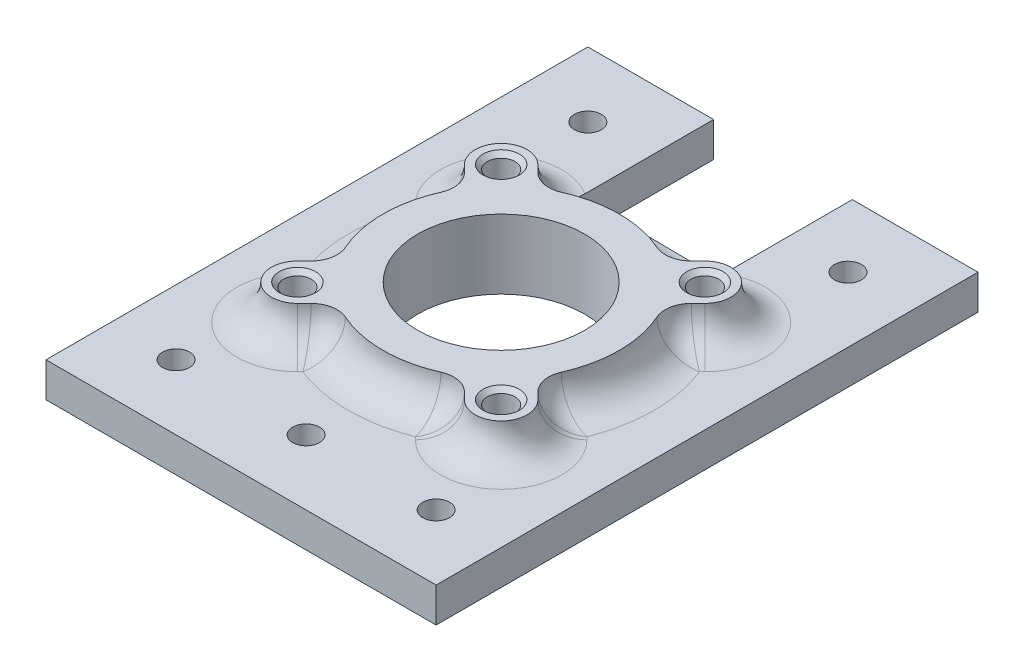
SolidWorks part; units mm, degrees
material "PET"
ref_plane "Front Plane" through (0, 0, 0) normal (0, 0, 1) x (1, 0, 0)
ref_plane "Top Plane" through (0, 0, 0) normal (0, 1, 0) x (1, 0, 0)
ref_plane "Right Plane" through (0, 0, 0) normal (1, 0, 0) x (0, 0, -1)
sketch "Sketch1" plane through (0, 0, 0) normal (0, 1, 0) x (1, 0, 0)
  line L1 (-45, 65) -> (45, 65)
  line L2 (-45, 65) -> (-45, -60)
  line L3 (-45, -60) -> (45, -60)
  line L4 (45, 65) -> (45, -60)
  circle A0 centre (0, 0) radius 19.25
  point P0 (0, 0)
  dimension "D4" = 38.5
  dimension "D1" = 90
  dimension "D2" = 125
  dimension "D3" = 45
  dimension "D5" = 65
extrude "Boss-Extrude1" add sketch "Sketch1" along normal blind 8
sketch "Sketch5" plane through (0, 8, 0) normal (0, 1, 0) x (1, 0, 0)
  circle A0 centre (0, 0) radius 19.25
  circle A1 centre (0, 0) radius 27.25
  dimension "D1" = 38.5
  dimension "D2" = 8
extrude "Boss-Extrude2" add sketch "Sketch5" along normal blind 8
sketch "Sketch9" plane through (0, 8, 0) normal (0, 1, 0) x (1, 0, 0)
  line L0 (17.6998, 26.1624) -> (19.2687, 27.7313)
  line L1 (-23.5, -23.5) -> (23.5, -23.5) construction
  line L2 (-23.5, -23.5) -> (-23.5, 23.5) construction
  line L3 (-23.5, 23.5) -> (23.5, 23.5) construction
  line L4 (23.5, -23.5) -> (23.5, 23.5) construction
  line L5 (-23.5, -23.5) -> (23.5, 23.5) construction
  line L6 (-23.5, 23.5) -> (23.5, -23.5) construction
  line L7 (19.2687, -27.7313) -> (17.6998, -26.1624)
  line L8 (27.7313, -19.2687) -> (26.1624, -17.6998)
  line L9 (-27.7313, -19.2687) -> (-26.1624, -17.6998)
  line L10 (-19.2687, -27.7313) -> (-17.6998, -26.1624)
  line L11 (-26.1624, 17.6998) -> (-27.7313, 19.2687)
  line L12 (-17.6998, 26.1624) -> (-19.2687, 27.7313)
  line L13 (26.1624, 17.6998) -> (27.7313, 19.2687)
  circle A1 centre (-23.5, -23.5) radius 5.984
  circle A2 centre (-23.5, 23.5) radius 5.984
  circle A3 centre (23.5, 23.5) radius 5.984
  circle A4 centre (23.5, -23.5) radius 5.984
  arc A5 (-24.9184, -11.0288) -> (-11.0288, -24.9184) centre (0, 0) ccw
  arc A6 (-11.0288, 24.9184) -> (-24.9184, 11.0288) centre (0, 0) ccw
  arc A7 (24.9184, 11.0288) -> (11.0288, 24.9184) centre (0, 0) ccw
  arc A8 (26.1624, -17.6998) -> (24.9184, -11.0288) centre (30.4051, -13.4571) cw
  arc A9 (17.6998, -26.1624) -> (11.0288, -24.9184) centre (13.4571, -30.4051) ccw
  arc A10 (-26.1624, -17.6998) -> (-24.9184, -11.0288) centre (-30.4051, -13.4571) ccw
  arc A11 (-17.6998, -26.1624) -> (-11.0288, -24.9184) centre (-13.4571, -30.4051) cw
  arc A12 (26.1624, 17.6998) -> (24.9184, 11.0288) centre (30.4051, 13.4571) ccw
  arc A13 (17.6998, 26.1624) -> (11.0288, 24.9184) centre (13.4571, 30.4051) cw
  arc A14 (-17.6998, 26.1624) -> (-11.0288, 24.9184) centre (-13.4571, 30.4051) ccw
  arc A15 (-26.1624, 17.6998) -> (-24.9184, 11.0288) centre (-30.4051, 13.4571) cw
  arc A16 (11.0288, -24.9184) -> (24.9184, -11.0288) centre (0, 0) ccw
  point P0 (0, 0)
  point P30 (23.0297, -14.567)
  point P41 (14.567, 23.0297)
  point P46 (-23.0297, 14.567)
  circle M29 centre (0, 0) radius 27.25
  dimension "D2" = 54.5
  dimension "D3" = 6
  dimension "D1" = 47
sketch "Sketch14" plane through (0, 8, 0) normal (0, 1, 0) x (1, 0, 0)
  line L0 (-45, 65) -> (-45, -60) construction
  line L1 (30, 50) -> (-30, 50) construction
  line L2 (30, 50) -> (30, -45) construction
  line L3 (30, -45) -> (-30, -45) construction
  line L4 (-30, 50) -> (-30, -45) construction
  line L5 (45, 65) -> (-45, 65) construction
  line L6 (45, -60) -> (45, 65) construction
  line L7 (-45, -60) -> (45, -60) construction
  point P0 (0, 0)
  point P15 (0, -45)
  point P18 (0, 65)
  dimension "D7" = 30
  dimension "D9" = 15
  dimension "D10" = 15
  dimension "D1" = 15
  dimension "D2" = 15
hole_wizard "Ø6.2 (6.2) Diameter Hole2" positions "Sketch15" profile "Sketch16" hole size "Ø6.2" standard "ANSI Metric" end condition through all
sketch "Sketch15" plane through (0, 8, 0) normal (0, 1, 0) x (1, 0, 0)
  point P6 (-30, 50)
  point P15 (30, 50)
  point P21 (0, -45)
  point P24 (30, -45)
  point P32 (-30, -45)
sketch "Sketch16" plane through (-30, 8, -50) normal (1, 0, 0) x (0, 0, 1)
  line L0 (0, 0) -> (0, 8)
  line L1 (0, 8) -> (3.1, 8)
  line L2 (3.1, 8) -> (3.1, 0)
  line L5 (3.1, 0) -> (0, 0)
  line L11 (0, -6.35) -> (0, 107.95) construction
  dimension "Thru Hole Dia." = 6.2
  dimension "Thru Hole Depth" = 8
extrude "Boss-Extrude6" add sketch "Sketch9" along normal blind 8 contours L11 A15 A2 M29 | A14 L12 A2 M29 | A2 | A12 L13 A3 M29 | L0 A13 A3 M29 | A3 | L10 A11 A1 M29 | A10 L9 A1 M29 | A1 | A9 L7 A4 M29 | L8 A8 A4 M29 | A4 region at (16.1538, 8, -23.5548) region at (23.5, 8, -23.5) region at (23.5548, 8, -16.1538) region at (-16.1538, 8, -23.5548) region at (-23.5548, 8, -16.1538) region at (-23.5, 8, -23.5) region at (23.5548, 8, 16.1538) region at (-23.5548, 8, 16.1538) region at (23.5, 8, 23.5) region at (16.1538, 8, 23.5548) region at (-16.1538, 8, 23.5548) region at (-23.5, 8, 23.5)
hole_wizard "Ø6.4 (6.4) Diameter Hole1" positions "Sketch19" profile "Sketch20" hole size "Ø6.4" standard "ANSI Metric" end condition through all
sketch "Sketch19" plane through (0, 16, 0) normal (0, 1, 0) x (1, 0, 0)
  point P0 (-23.5, -23.5)
  point P3 (23.5, -23.5)
  point P6 (23.5, 23.5)
  point P9 (-23.5, 23.5)
sketch "Sketch20" plane through (-23.5, 16, 23.5) normal (1, 0, 0) x (0, 0, 1)
  line L0 (0, 0) -> (0, 16)
  line L1 (0, 16) -> (3.2, 16)
  line L2 (3.2, 16) -> (3.2, 0)
  line L5 (3.2, 0) -> (0, 0)
  line L11 (0, -6.35) -> (0, 107.95) construction
  dimension "Thru Hole Dia." = 6.4
  dimension "Thru Hole Depth" = 16
fillet "Fillet1" radius 8 24 edges at (26.9469, 8, -18.4842) (27.7313, 8, -27.7313) (18.4842, 8, -26.9469) (14.557, 8, -24.5068) (0, 8, -27.25) (-14.557, 8, -24.5068) (-18.4842, 8, -26.9469) (-27.7313, 8, -27.7313) (-26.9469, 8, -18.4842) (-24.5068, 8, -14.557) (-27.25, 8, 0) (-24.5068, 8, 14.557) (-26.9469, 8, 18.4842) (-27.7313, 8, 27.7313) (-18.4842, 8, 26.9469) (-14.557, 8, 24.5068) (0, 8, 27.25) (14.557, 8, 24.5068) (18.4842, 8, 26.9469) (27.7313, 8, 27.7313) (26.9469, 8, 18.4842) (24.5068, 8, 14.557) (27.25, 8, 0) (24.5068, 8, -14.557)
chamfer "Chamfer3" distance 1 angle 45 4 edges at (23.5, 16, -20.3) (23.5, 16, 26.7) (-23.5, 16, 26.7) (-23.5, 16, -20.3)
sketch "Sketch21" plane through (0, 0, 0) normal (0, -1, 0) x (1, 0, 0)
  line L0 (45, -65) -> (-45, -65) construction
  line L1 (-16, -65) -> (16, -65)
  line L2 (-16, -65) -> (-16, -34)
  line L3 (-16, -34) -> (16, -34)
  line L4 (16, -65) -> (16, -34)
  line L5 (0, 0) -> (0, -65) construction
  dimension "D1" = 32
  dimension "D2" = 31
extrude "Cut-Extrude1" cut sketch "Sketch21" against normal through all
